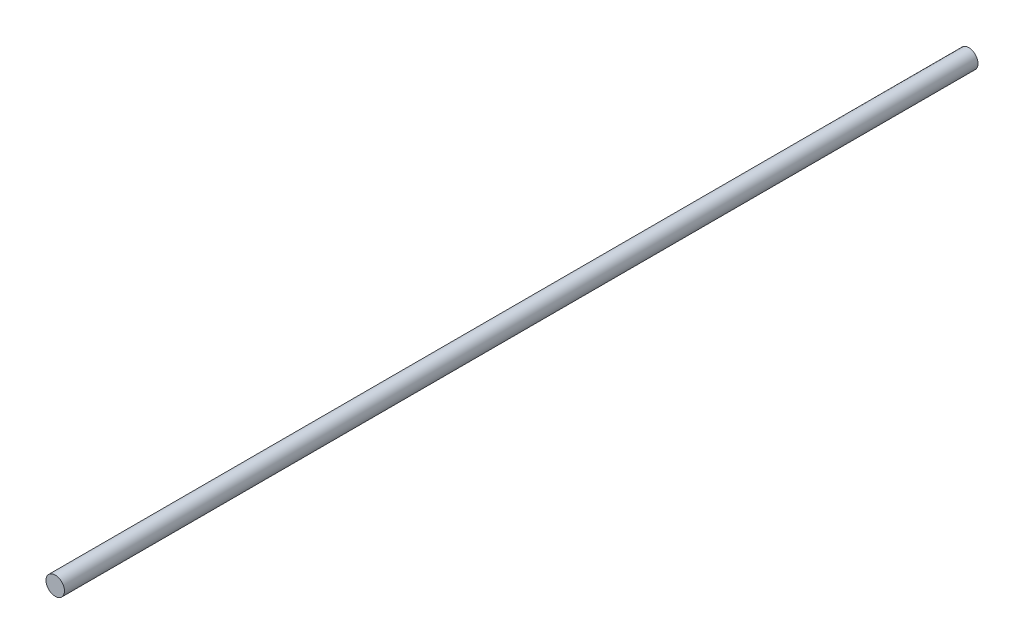
SolidWorks part; units mm, degrees
material "AISI 316 Stainless Steel Sheet (SS)"
ref_plane "Front (1)" through (0, 0, 0) normal (0, 0, 1) x (1, 0, 0)
ref_plane "Top (2)" through (0, 0, 0) normal (0, 1, 0) x (1, 0, 0)
ref_plane "Right (3)" through (0, 0, 0) normal (1, 0, 0) x (0, 0, -1)
ref_axis "X Axis" through (13.5064, 0, 0) along (-1, 0, 0)
ref_axis "Y Axis" through (0, 12.3593, 0) along (0, -1, 0)
ref_axis "Z Axis" through (0, 0, 14.1119) along (0, 0, -1)
sketch "Sketch2" plane through (0, 0, 0) normal (1, 0, 0) x (0, 0, -1)
  line L1 (0, 0) -> (395, 0)
  line L2 (0, 0) -> (0, 4)
  line L3 (0, 4) -> (395, 4)
  line L4 (395, 0) -> (395, 4)
  dimension "D1" = 395
  dimension "D2" = 4
revolve "Revolve1" add sketch "Sketch2" angle 360 about L1
